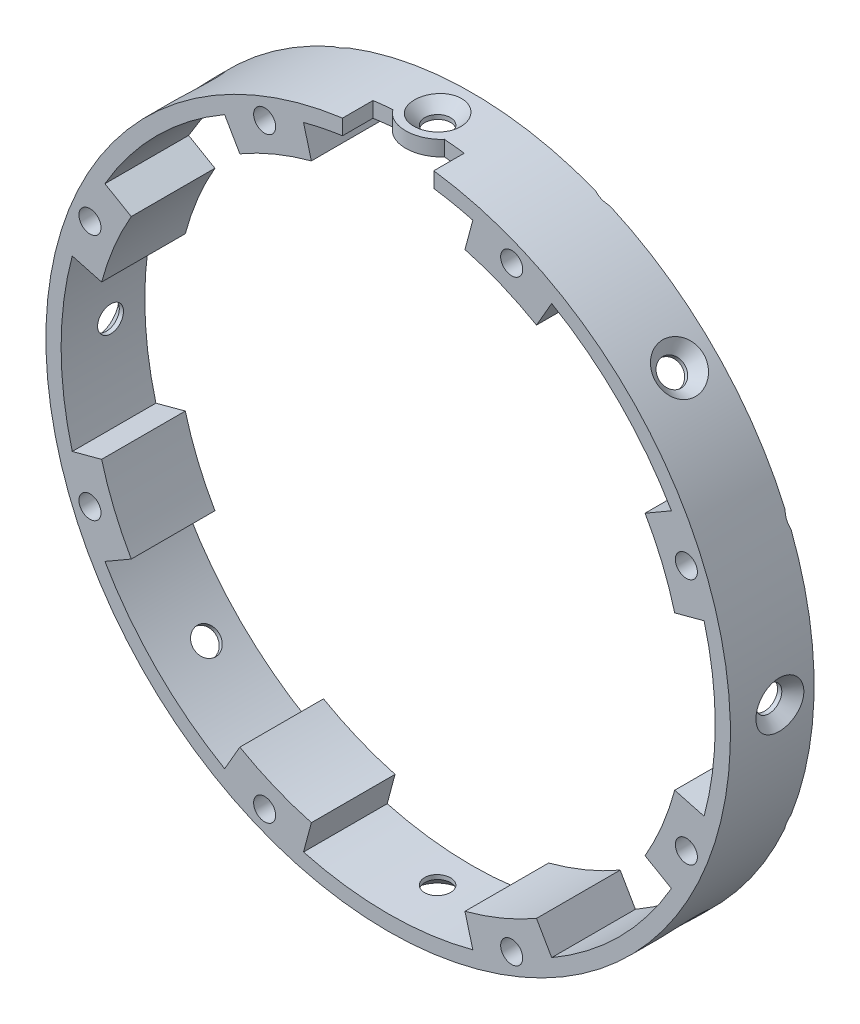
SolidWorks part; units mm, degrees
ref_plane "前视基准面" through (0, 0, 0) normal (0, 0, 1) x (1, 0, 0)
ref_plane "上视基准面" through (0, 0, 0) normal (0, 1, 0) x (1, 0, 0)
ref_plane "右视基准面" through (0, 0, 0) normal (1, 0, 0) x (0, 0, -1)
sketch "草图1" plane through (0, 0, 0) normal (0, 0, 1) x (1, 0, 0)
  line L0 (11.1292, 41.5348) -> (10.0939, 37.6711)
  line L17 (21.5, 37.2391) -> (19.5, 33.775)
  line L18 (-11.1292, 41.5348) -> (-10.0939, 37.6711)
  line L19 (37.2391, 21.5) -> (33.775, 19.5)
  line L20 (41.5348, 11.1292) -> (37.6711, 10.0939)
  line L21 (41.5348, -11.1292) -> (37.6711, -10.0939)
  line L22 (37.2391, -21.5) -> (33.775, -19.5)
  line L23 (21.5, -37.2391) -> (19.5, -33.775)
  line L24 (11.1292, -41.5348) -> (10.0939, -37.6711)
  line L25 (-11.1292, -41.5348) -> (-10.0939, -37.6711)
  line L26 (-21.5, -37.2391) -> (-19.5, -33.775)
  line L27 (-37.2391, -21.5) -> (-33.775, -19.5)
  line L28 (-41.5348, -11.1292) -> (-37.6711, -10.0939)
  line L29 (-41.5348, 11.1292) -> (-37.6711, 10.0939)
  line L30 (-37.2391, 21.5) -> (-33.775, 19.5)
  line L31 (-21.5, 37.2391) -> (-19.5, 33.775)
  circle A1 centre (0, 0) radius 45
  arc A3 (10.0939, 37.6711) -> (19.5, 33.775) centre (0, 0) cw
  arc A4 (11.1292, 41.5348) -> (-11.1292, 41.5348) centre (0, 0) ccw
  arc A21 (37.2391, 21.5) -> (21.5, 37.2391) centre (0, 0) ccw
  arc A22 (33.775, 19.5) -> (37.6711, 10.0939) centre (0, 0) cw
  arc A23 (41.5348, -11.1292) -> (41.5348, 11.1292) centre (0, 0) ccw
  arc A24 (37.6711, -10.0939) -> (33.775, -19.5) centre (0, 0) cw
  arc A25 (21.5, -37.2391) -> (37.2391, -21.5) centre (0, 0) ccw
  arc A26 (19.5, -33.775) -> (10.0939, -37.6711) centre (0, 0) cw
  arc A27 (-11.1292, -41.5348) -> (11.1292, -41.5348) centre (0, 0) ccw
  arc A28 (-10.0939, -37.6711) -> (-19.5, -33.775) centre (0, 0) cw
  arc A29 (-37.2391, -21.5) -> (-21.5, -37.2391) centre (0, 0) ccw
  arc A30 (-33.775, -19.5) -> (-37.6711, -10.0939) centre (0, 0) cw
  arc A31 (-41.5348, 11.1292) -> (-41.5348, -11.1292) centre (0, 0) ccw
  arc A32 (-37.6711, 10.0939) -> (-33.775, 19.5) centre (0, 0) cw
  arc A33 (-21.5, 37.2391) -> (-37.2391, 21.5) centre (0, 0) ccw
  arc A34 (-19.5, 33.775) -> (-10.0939, 37.6711) centre (0, 0) cw
  point P51 (0, 0)
  point P56 (0, 0)
  dimension "D1" = 8
extrude "凸台-拉伸1" add sketch "草图1" against normal blind 11
hole_wizard "M3 锥坑平头的锥孔2" positions "3D草图3" profile "草图4" countersink size "M3" standard "BSI" end condition through all
sketch3d "3D草图3"
  point P67 (31.8198, 31.8198, -6.5)
  point P76 (45, 0, -6.5)
  point P83 (31.8198, -31.8198, -6.5)
  point P85 (-31.8198, 31.8198, -6.5)
  point P87 (-31.8198, -31.8198, -6.5)
  point P96 (0, -45, -6.5)
  point P98 (0, 45, -6.5)
  point P105 (-45, 0, -6.5)
sketch "草图4" plane through (31.8198, 31.8198, -6.5) normal (0, 0, 1) x (-0.7071, 0.7071, 0)
  line L0 (0, 0) -> (0, 108.6396)
  line L1 (0, 108.6396) -> (1.7, 108.6396)
  line L2 (1.7, 108.6396) -> (1.7, 1.45)
  line L3 (1.7, 1.45) -> (3.15, 0)
  line L5 (3.15, 0) -> (0, 0)
  line L6 (-1.7, 1.45) -> (-3.15, 0) construction
  line L11 (0, -6.35) -> (0, 107.95) construction
  dimension "通孔孔直径" = 3.4
  dimension "通孔孔深度" = 108.6396
  dimension "近端锥形沉头孔直径" = 6.3
  dimension "近端锥形沉头孔角度" = 90
ref_plane "基准面1" through (0, 45, 0) normal (0, 1, 0) x (1, 0, 0)
sketch "草图7" plane through (0, 45, 0) normal (0, 1, 0) x (1, 0, 0)
  line L0 (-6, 0) -> (6, 0)
  line L1 (-45, 0) -> (45, 0) construction
  line L2 (6, 0) -> (6, 4)
  line L3 (6, 4) -> (3.3749, 4)
  line L5 (-6, 0) -> (-6, 4)
  line L6 (-6, 4) -> (-3.3749, 4)
  arc A1 (3.3749, 4) -> (-3.3749, 4) centre (0, 6.5) cw
extrude "切除-拉伸1" cut sketch "草图7" against normal up to next
hole_wizard "M2.5 锥坑平头的锥孔2" positions "3D草图4" profile "草图8" countersink size "M2.5" standard "BSI" end condition up to next
sketch3d "3D草图4"
  point P13 (39.2044, 16.239, -11)
  point P19 (16.239, 39.2044, -11)
  point P21 (-16.239, 39.2044, -11)
  point P23 (39.2044, -16.239, -11)
  point P26 (-39.2044, 16.239, -11)
  point P28 (-39.2044, -16.239, -11)
  point P30 (-16.239, -39.2044, -11)
  point P32 (16.239, -39.2044, -11)
  point P34 (0, 0, 0)
  point P35 (0, 0, 0)
  point P36 (0, 0, 0)
  point P37 (0, 0, 0)
  point P38 (0, 0, 0)
  point P39 (0, 0, 0)
  point P40 (0, 0, 0)
  point P41 (0, 0, 0)
  point P42 (0, 0, 0)
  point P43 (0, 0, 0)
  point P44 (0, 0, 0)
  point P45 (0, 0, 0)
  point P46 (0, 0, 0)
  point P47 (0, 0, 0)
  point P48 (0, 0, 0)
  point P49 (0, 0, 0)
  point P50 (0, 0, 0)
  point P51 (0, 0, 0)
sketch "草图8" plane through (39.2044, 16.239, -11) normal (1, 0, 0) x (0, 1, 0)
  line L0 (0, 0) -> (0, 11)
  line L1 (0, 11) -> (1.45, 11)
  line L2 (1.45, 11) -> (1.45, 1.3)
  line L3 (1.45, 1.3) -> (2.75, 0)
  line L5 (2.75, 0) -> (0, 0)
  line L6 (-1.45, 1.3) -> (-2.75, 0) construction
  line L11 (0, -6.35) -> (0, 107.95) construction
  dimension "通孔孔直径" = 2.9
  dimension "通孔孔深度" = 11
  dimension "近端锥形沉头孔直径" = 5.5
  dimension "近端锥形沉头孔角度" = 90
